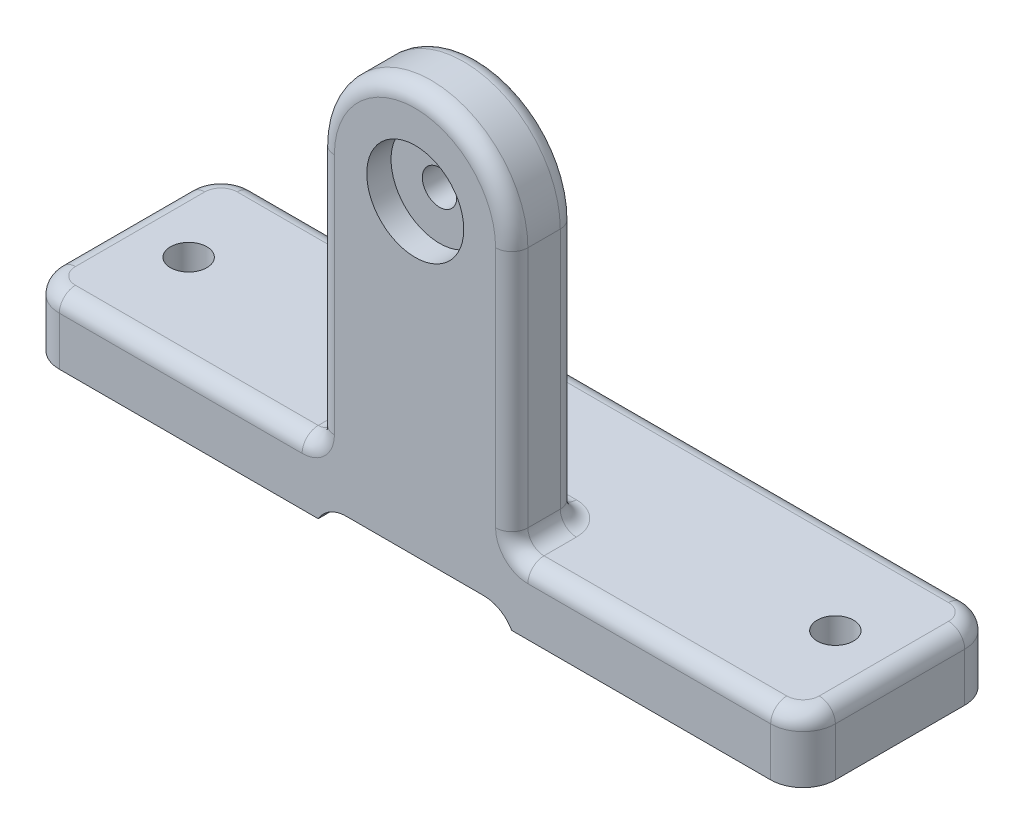
SolidWorks part; units mm, degrees
ref_plane "Front Plane" through (0, 0, 0) normal (0, 0, 1) x (1, 0, 0)
ref_plane "Top Plane" through (0, 0, 0) normal (0, 1, 0) x (1, 0, 0)
ref_plane "Right Plane" through (0, 0, 0) normal (1, 0, 0) x (0, 0, -1)
sketch "Sketch1" plane through (0, 0, 0) normal (0, 1, 0) x (1, 0, 0)
  line L1 (0, 0) -> (152.4, 0)
  line L2 (0, 0) -> (0, 38.1)
  line L3 (0, 38.1) -> (152.4, 38.1)
  line L4 (152.4, 0) -> (152.4, 38.1)
  dimension "D1" = 152.4
  dimension "D2" = 38.1
extrude "BasePlate" add sketch "Sketch1" along normal blind 12.7
sketch "Sketch3" plane through (0, 0, 0) normal (0, 0, 1) x (1, 0, 0)
  line L0 (57.2, 0) -> (57.2, 63.5)
  line L1 (0, 0) -> (152.4, 0) construction
  line L2 (95.2, 63.5) -> (95.2, 0)
  line L3 (0, 12.7) -> (0, 0) construction
  line L8 (0, 0) -> (152.4, 0)
  line L9 (152.4, 0) -> (152.4, 12.7)
  line L10 (152.4, 12.7) -> (0, 12.7)
  line L11 (0, 12.7) -> (0, 0)
  line L12 (57.2, 0) -> (95.2, 0)
  arc A0 (57.2, 63.5) -> (95.2, 63.5) centre (76.2, 63.5) cw
  dimension "D1" = 19
  dimension "D2" = 63.5
  dimension "D3" = 76.2
  dimension "D4" = 0
extrude "VertBoss" add sketch "Sketch3" against normal blind 12.7
hole_wizard "9/32 (0.28125) Diameter Hole1" positions "Sketch4" profile "Sketch5" hole size "9/32" standard "ANSI Inch" end condition through all
sketch "Sketch4" plane through (0, 12.7, 0) normal (0, 1, 0) x (1, 0, 0)
  line L0 (0, 38.1) -> (0, 0) construction
  line L1 (152.4, 0) -> (152.4, 38.1) construction
  line L2 (152.4, 38.1) -> (0, 38.1) construction
  point P0 (139.7, 19.05)
  point P2 (12.7, 19.05)
  dimension "D1" = 12.7
  dimension "D2" = 12.7
  dimension "D3" = 19.05
  dimension "D4" = 19.05
sketch "Sketch5" plane through (139.7, 12.7, -19.05) normal (1, 0, 0) x (0, 0, 1)
  line L0 (0, 0) -> (0, 12.7)
  line L1 (0, 12.7) -> (3.5719, 12.7)
  line L2 (3.5719, 12.7) -> (3.5719, 0)
  line L5 (3.5719, 0) -> (0, 0)
  line L11 (0, -6.35) -> (0, 107.95) construction
  dimension "Thru Hole Dia." = 7.1437
  dimension "Thru Hole Depth" = 12.7
hole_wizard "CBORE for 1/4 Hex Head Bolt1" positions "Sketch9" profile "Sketch10" counterbore size "1/4" standard "ANSI Inch" end condition through all
sketch "Sketch9" plane through (0, 0, 0) normal (0, 0, 1) x (1, 0, 0)
  point P0 (76.2471, 63.4871)
sketch "Sketch10" plane through (76.2471, 63.4871, 0) normal (1, 0, 0) x (0, -1, 0)
  line L0 (0, 0) -> (0, 38.1)
  line L1 (0, 38.1) -> (3.3782, 38.1)
  line L3 (3.3782, 38.1) -> (3.3782, 4.7752)
  line L4 (3.3782, 4.7752) -> (9.525, 4.7752)
  line L5 (9.525, 4.7752) -> (9.525, 0)
  line L7 (9.525, 0) -> (0, 0)
  line L11 (0, -6.35) -> (0, 107.95) construction
  dimension "Thru Hole Dia." = 6.7564
  dimension "Thru Hole Depth" = 38.1
  dimension "C'Bore Dia." = 19.05
  dimension "C'Bore Depth" = 4.7752
sketch "Sketch11" plane through (0, 0, 0) normal (0, 0, 1) x (1, 0, 0)
  line L0 (0, 0) -> (152.4, 0) construction
  line L1 (57.2, 0) -> (95.2, 0)
  line L2 (57.2, 0) -> (57.2, 3.17)
  line L3 (57.2, 3.17) -> (95.2, 3.17)
  line L4 (95.2, 0) -> (95.2, 3.17)
  line L5 (57.2, 63.5) -> (57.2, 12.7) construction
  line L6 (95.2, 12.7) -> (95.2, 63.5) construction
  dimension "D1" = 3.17
extrude "BottomSlot" cut sketch "Sketch11" against normal through all
fillet "Fillet1" radius 6.35 6 edges at (95.2, 3.17, -19.05) (57.2, 3.17, -19.05) (0, 6.35, -38.1) (0, 6.35, 0) (152.4, 6.35, -38.1) (152.4, 6.35, 0)
fillet "Fillet2" radius 3.17 18 edges at (57.2, 12.7, -6.35) (95.2, 12.7, -6.35) (76.2, 12.7, -12.7) (95.2, 38.1, -12.7) (57.2, 38.1, -12.7) (76.2, 82.5, -12.7) (1.8599, 12.7, -36.2401) (0, 12.7, -19.05) (1.8599, 12.7, -1.8599) (76.2, 12.7, -38.1) (150.5401, 12.7, -36.2401) (152.4, 12.7, -19.05) (150.5401, 12.7, -1.8599) (120.625, 12.7, 0) (31.775, 12.7, 0) (95.2, 38.1, 0) (57.2, 38.1, 0) (76.2, 82.5, 0)
